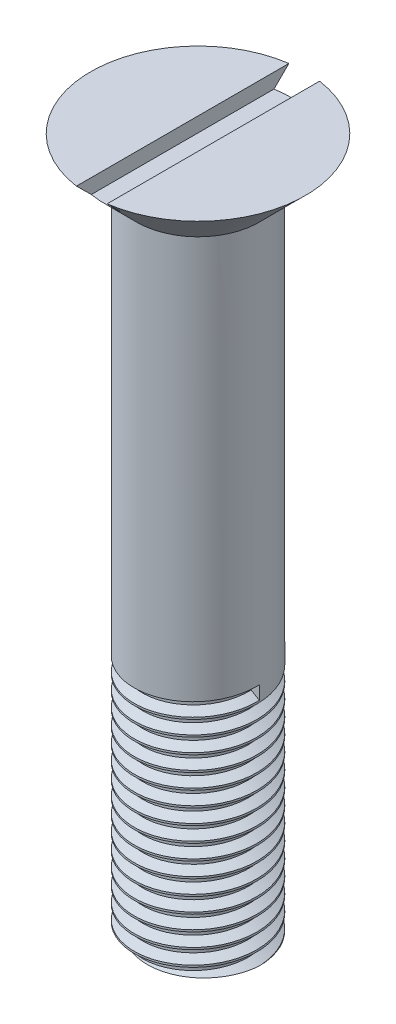
SolidWorks part; units mm, degrees
ref_plane "Front Plane" through (0, 0, 0) normal (0, 0, 1) x (1, 0, 0)
ref_plane "Top Plane" through (0, 0, 0) normal (0, 1, 0) x (1, 0, 0)
ref_plane "Right Plane" through (0, 0, 0) normal (1, 0, 0) x (0, 0, -1)
sketch "Sketch1" plane through (0, 0, 0) normal (0, 0, 1) x (1, 0, 0)
  line L0 (0, 0) -> (0, 45) construction
  line L1 (0, 45) -> (7, 45)
  line L2 (7, 45) -> (4, 42)
  line L3 (4, 42) -> (4, 0)
  line L4 (4, 0) -> (0, 0)
  line L5 (0, 0) -> (0, 45)
  dimension "D1" = 45
  dimension "D2" = 8
  dimension "D3" = 45
  dimension "D4" = 3
revolve "Revolve1" add sketch "Sketch1" angle 360 about L0
thread "Thread1" pitch 1 method cut trim with start face yes profile "Thread Profile1" start angle 0, offset 2, length 17, pitch 1, diameter 8
ref_plane "Plane1" through (4, -2, 0) normal (0, 0, 1) x (1, 0, 0)
sketch "Thread Profile1" plane through (4, -2, 0) normal (0, 0, 1) x (1, 0, 0)
  line L0 (0, 0) -> (0, 1) construction
  line L11 (0, 0) -> (0, 0.875)
  line L12 (0, 0.875) -> (-0.5413, 0.5625)
  line L13 (-0.5413, 0.5625) -> (-0.5413, 0.3125)
  line L15 (-0.5413, 0.3125) -> (0, 0)
  line L17 (-0.5413, 0.4375) -> (0, 0.4375) construction
  point P2 (0, 0)
  dimension "Pitch" = 1
  dimension "Profile_Angle" = 60
  dimension "Profile_Land" = 0.25
  dimension "Profile_Height" = 0.5413
sketch "Sketch5" plane through (0, 45, 0) normal (0, 1, 0) x (1, 0, 0)
  line L1 (-1, -8.9399) -> (1, -8.9399)
  line L2 (-1, -8.9399) -> (-1, 8.9399)
  line L3 (-1, 8.9399) -> (1, 8.9399)
  line L4 (1, -8.9399) -> (1, 8.9399)
  line L5 (-1, -8.9399) -> (1, 8.9399) construction
  line L6 (-1, 8.9399) -> (1, -8.9399) construction
  point P0 (0, 0)
  dimension "D1" = 2
extrude "Cut-Extrude1" cut sketch "Sketch5" against normal blind 0.96
